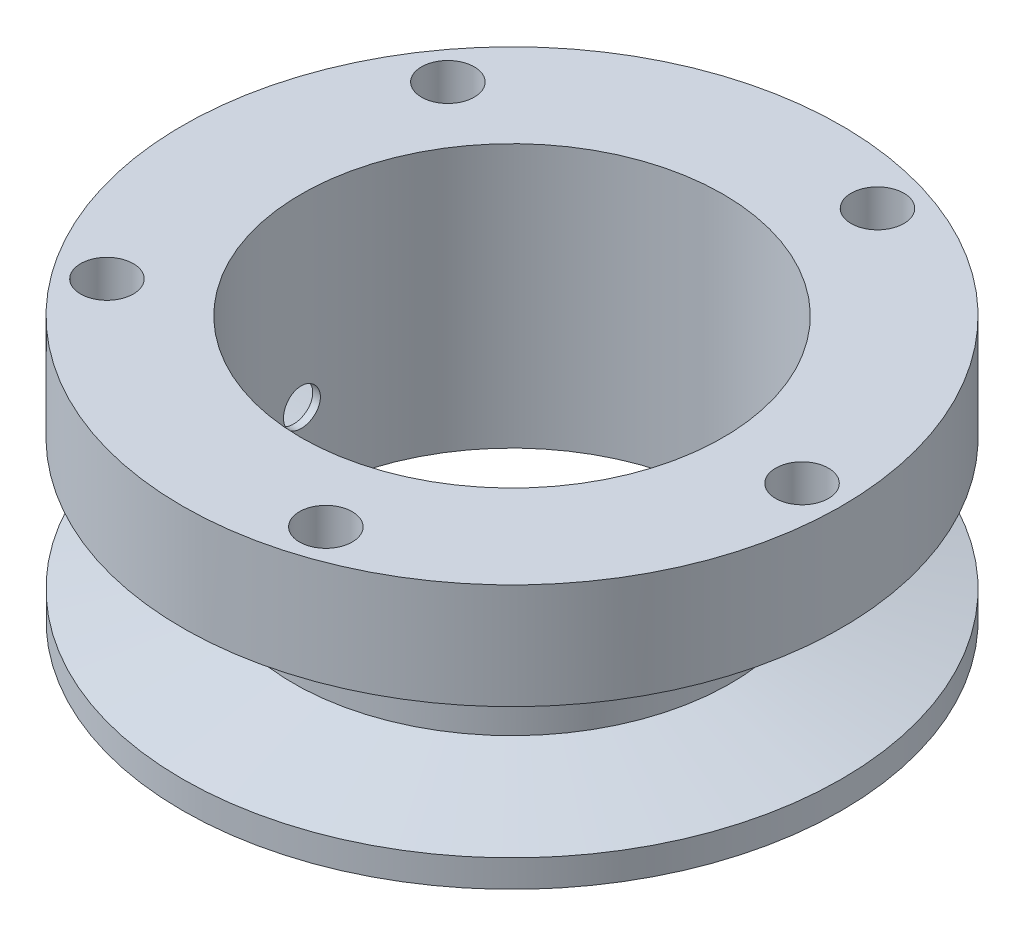
SolidWorks part; units mm, degrees
ref_plane "前视基准面" through (0, 0, 0) normal (0, 0, 1) x (1, 0, 0)
ref_plane "上视基准面" through (0, 0, 0) normal (0, 1, 0) x (1, 0, 0)
ref_plane "右视基准面" through (0, 0, 0) normal (1, 0, 0) x (0, 0, -1)
sketch "草图1" plane through (0, 0, 0) normal (0, 1, 0) x (1, 0, 0)
  circle A0 centre (0, 0) radius 12.5
extrude "凸台-拉伸1" add sketch "草图1" along normal blind 4
sketch "草图2" plane through (0, 4, 0) normal (0, 1, 0) x (1, 0, 0)
  circle A0 centre (0, 0) radius 10 construction
  circle A1 centre (10, 0) radius 1
  circle A2 centre (3.3992, -10.4616) radius 1
  circle A3 centre (-8.5902, -7.4167) radius 1
  circle A4 centre (-9.3992, 4.9268) radius 1
  circle A5 centre (2.0902, 9.5106) radius 1
  point P15 (-0.5, -0.6882)
  dimension "D1" = 5
extrude "凸台-拉伸2" add sketch "草图2" along normal blind 7.5
sketch "草图4" plane through (0, 4, 0) normal (0, 1, 0) x (1, 0, 0)
  circle A0 centre (0, 0) radius 12.5
sketch "草图5" plane through (0, 4, 0) normal (0, 1, 0) x (1, 0, 0)
  circle A0 centre (0, 0) radius 6
extrude "切除-拉伸1" cut sketch "草图5" against normal blind 10
sketch "草图7" plane through (0, 11.5, 0) normal (0, 1, 0) x (1, 0, 0)
  circle A0 centre (-8.5902, -7.4167) radius 1 construction
  circle A1 centre (-9.3992, 4.9268) radius 1 construction
  circle A2 centre (2.0902, 9.5106) radius 1 construction
  circle A3 centre (10, 0) radius 1 construction
  circle A4 centre (3.3992, -10.4616) radius 1 construction
  circle A5 centre (-8.5902, -7.4167) radius 1
  circle A6 centre (-9.3992, 4.9268) radius 1
  circle A7 centre (2.0902, 9.5106) radius 1
  circle A8 centre (10, 0) radius 1
  circle A9 centre (3.3992, -10.4616) radius 1
extrude "切除-拉伸2" cut sketch "草图7" against normal up to surface (7.5 mm away) contours A6 up to face at (0, 4, 6)
sketch "草图8" plane through (0, 4, 0) normal (0, 1, 0) x (1, 0, 0)
  circle A0 centre (0, 0) radius 6 construction
  circle A1 centre (0, 0) radius 12.5
  circle A2 centre (0, 0) radius 12.5
  circle A3 centre (0, 0) radius 6
  dimension "D1" = 0
extrude "切除-拉伸3" cut sketch "草图8" along normal blind 10
sketch "草图9" plane through (0, 4, 0) normal (0, 1, 0) x (1, 0, 0)
  circle A0 centre (11, 0) radius 1
  circle A1 centre (3.3992, -10.4616) radius 1
  circle A2 centre (-8.8992, -6.4656) radius 1
  circle A3 centre (-8.8992, 6.4656) radius 1
  circle A4 centre (3.3992, 10.4616) radius 1
  point P14 (0, 0)
  dimension "D1" = 5
extrude "凸台-拉伸3" add sketch "草图9" along normal blind 10
sketch "草图10" plane through (0, 14, 0) normal (0, 1, 0) x (1, 0, 0)
  circle A0 centre (3.3992, -10.4616) radius 1 construction
  circle A1 centre (-8.8992, -6.4656) radius 1
  circle A2 centre (-8.8992, -6.4656) radius 1
  circle A3 centre (11, 0) radius 1 construction
  circle A4 centre (3.3992, 10.4616) radius 1 construction
  circle A5 centre (-8.8992, 6.4656) radius 1 construction
  circle A6 centre (3.3992, -10.4616) radius 1
  circle A7 centre (11, 0) radius 1
  circle A8 centre (3.3992, 10.4616) radius 1
  circle A9 centre (-8.8992, 6.4656) radius 1
  dimension "D1" = 0
extrude "切除-拉伸4" cut sketch "草图10" against normal blind 14
sketch "草图11" plane through (0, 4, 0) normal (0, 1, 0) x (1, 0, 0)
  circle A0 centre (0, 0) radius 8
extrude "切除-拉伸5" cut sketch "草图11" against normal blind 10
sketch "草图12" plane through (0, 4, 0) normal (0, 1, 0) x (1, 0, 0)
  arc A0 (-1.4698, 12.4133) -> (-6.1073, 10.9065) centre (0, 0) ccw
  arc A1 (-1.4698, 12.4133) -> (8.4854, 9.1787) centre (4.9443, 15.2169) ccw
  arc A2 (11.3516, 5.2337) -> (11.3516, -5.2337) centre (16, 0) ccw
  arc A3 (8.4854, -9.1787) -> (-1.4698, -12.4133) centre (4.9443, -15.2169) ccw
  arc A4 (-6.1073, -10.9065) -> (-12.2599, -2.4381) centre (-12.9443, -9.4046) ccw
  arc A5 (-12.2599, 2.4381) -> (-6.1073, 10.9065) centre (-12.9443, 9.4046) ccw
  arc A6 (-6.1073, -10.9065) -> (-1.4698, -12.4133) centre (0, 0) ccw
  arc A7 (-12.2599, 2.4381) -> (-12.2599, -2.4381) centre (0, 0) ccw
  arc A8 (8.4854, -9.1787) -> (8.4854, 9.1787) centre (0, 0) ccw
  point P20 (0, 0)
  circle M4 centre (0, 0) radius 8
  circle M10 centre (0, 0) radius 12.5
  dimension "D1" = 5
extrude "凸台-拉伸4" add sketch "草图12" against normal blind 10 contours A5 A4 A3 A2 A1 M10 M4 | M4 region at (2.6748, 4, -8.2321) region at (0, 4, 0)
sketch "草图14" plane through (0, -6, 0) normal (0, -1, 0) x (1, 0, 0)
  circle A0 centre (0, 0) radius 8
extrude "切除-拉伸6" cut sketch "草图14" against normal blind 10
sketch "草图15" plane through (0, 0, 0) normal (1, 0, 0) x (0, 0, -1)
  line L0 (0, 0) -> (0, -3.9326) construction
  line L1 (12.4133, -6) -> (12.4133, 0) construction
  line L2 (12.4133, -5) -> (9.1787, -3.9326)
  line L3 (9.1787, -6) -> (9.1787, 0) construction
  line L4 (9.1787, -3.9326) -> (9.1787, -2.0674)
  line L5 (12.5, -1) -> (12.5, -5)
  line L6 (12.4133, -1) -> (9.1787, -2.0674)
  line L7 (12.4133, -5) -> (12.5, -5)
  line L8 (12.4133, -1) -> (12.4133, -5)
  line L9 (12.4133, -1) -> (12.5, -1)
revolve "切除-旋转2" cut sketch "草图15" angle 360 about L0 region at (0, -3, -12.4566) region at (0, -3, -10.9922)
sketch "草图16" plane through (0, 0, 0) normal (1, 0, 0) x (0, 0, -1)
  circle A0 centre (0, -3) radius 0.7
extrude "切除-拉伸7" cut sketch "草图16" against normal blind 10
sketch "草图17" plane through (0, 0, 0) normal (1, 0, 0) x (0, 0, -1)
  line L4 (12.5, -1) -> (9.2659, -2.0674)
  line L5 (0, 0) -> (0, 6.6443) construction
  line L6 (12.5, 0) -> (8.289, -2.0674)
  line L7 (12.5, 0) -> (12.5, -1)
  line L8 (8.289, -2.0674) -> (9.2659, -2.0674)
revolve "切除-旋转4" cut sketch "草图17" angle 360 about L5
sketch "草图18" plane through (0, -6, 0) normal (0, -1, 0) x (1, 0, 0)
  circle A0 centre (0, 0) radius 12.5
extrude "凸台-拉伸5" add sketch "草图18" against normal blind 2.07
sketch "草图19" plane through (0, 0, 0) normal (1, 0, 0) x (0, 0, -1)
  line L0 (12.5, -5.9555) -> (12.5, -4.965)
  line L1 (12.5, -6) -> (12.5, -3.93) construction
  line L2 (12.5, -6) -> (12.5, -3.93) construction
  line L3 (12.5, -4.965) -> (8.289, -3.93)
  line L4 (8.289, -3.93) -> (8.289, -2.0674)
  line L5 (8.289, -2.0674) -> (12.5, -2.0674)
  line L6 (12.5, -2.0674) -> (12.5, -4.965)
  line L7 (0, 0) -> (0, 5.4734) construction
revolve "切除-旋转5" cut sketch "草图19" angle 360 about L7 region at (0, -3.2762, -10.5471)
sketch "草图20" plane through (0, -3.93, 0) normal (0, 1, 0) x (1, 0, 0)
  circle A1 centre (0, 0) radius 8
  circle A2 centre (0, 0) radius 8
  dimension "D1" = 0
extrude "切除-拉伸8" cut sketch "草图20" against normal blind 2.07
